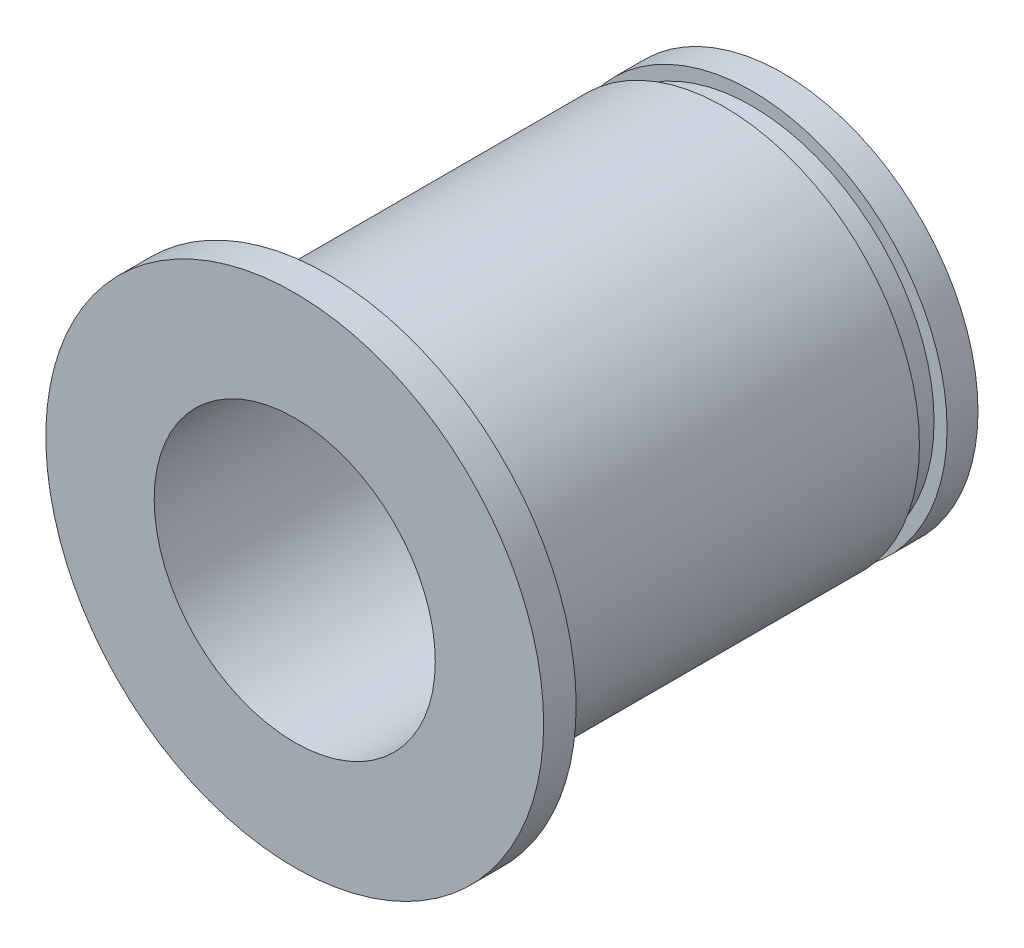
SolidWorks part; units mm, degrees
ref_plane "Front Plane" through (0, 0, 0) normal (0, 0, 1) x (1, 0, 0)
ref_plane "Top Plane" through (0, 0, 0) normal (0, 1, 0) x (1, 0, 0)
ref_plane "Right Plane" through (0, 0, 0) normal (1, 0, 0) x (0, 0, -1)
sketch "S01 - Ground guide bore and body" plane through (0, 0, 0) normal (0, 0, 1) x (1, 0, 0)
  circle A0 centre (0, 0) radius 6
  circle A1 centre (0, 0) radius 4.32
  dimension "D1" = 8.64
  dimension "D2" = 12
extrude "01 - Ground guide bore and body" add sketch "S01 - Ground guide bore and body" along normal blind 14 from offset 2 offset against normal yes
sketch "S02 - Outboard flange" plane through (0, 0, 0) normal (0, 0, 1) x (1, 0, 0)
  circle A0 centre (0, 0) radius 7.65
  circle A1 centre (0, 0) radius 4.32
  dimension "D1" = 8.64
  dimension "D2" = 15.3
extrude "02 - Outboard flange" add sketch "S02 - Outboard flange" along normal blind 1 from offset 12
sketch "S03 - External retaining ring groove" plane through (0, 0, 0) normal (0, 0, 1) x (1, 0, 0)
  circle A0 centre (0, 0) radius 6.1
  circle A1 centre (0, 0) radius 5.6
  dimension "D1" = 11.2
  dimension "D2" = 12.2
extrude "03 - External retaining ring groove" cut sketch "S03 - External retaining ring groove" along normal blind 0.85 from offset 1.05 offset against normal yes
